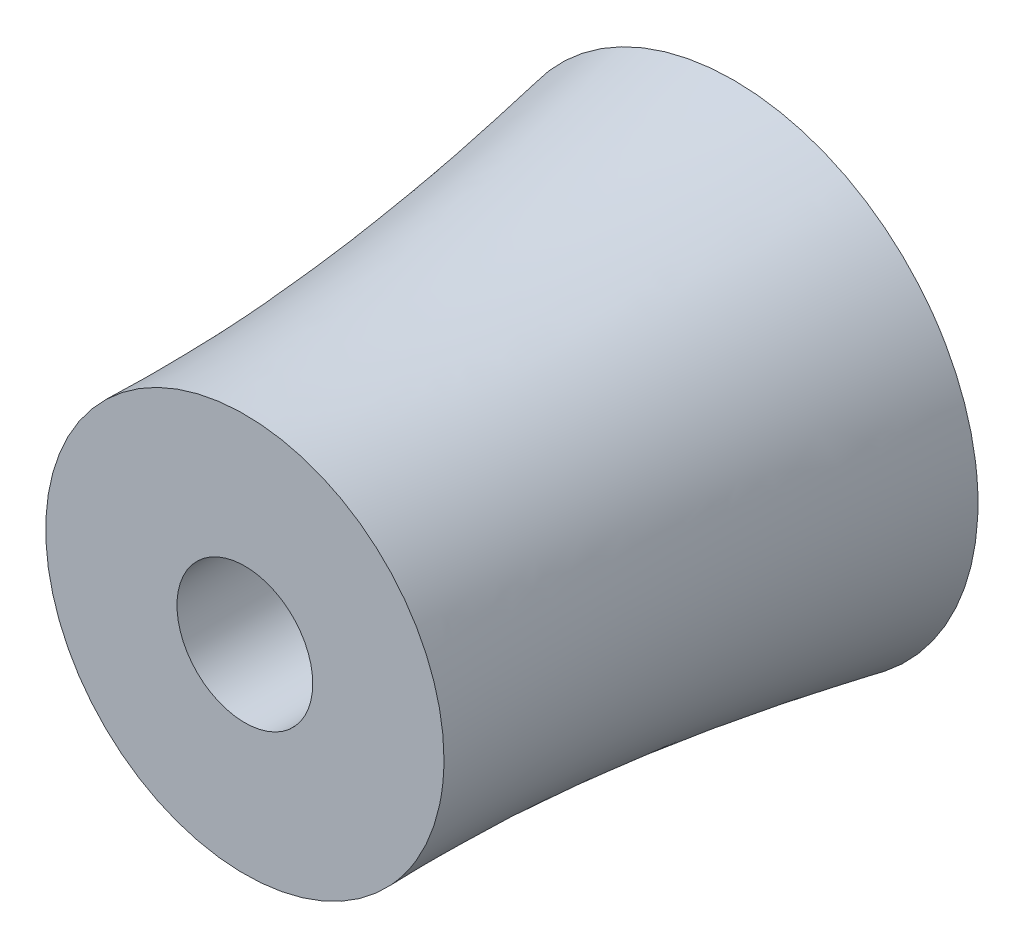
SolidWorks part; units mm, degrees
ref_plane "Plan de face" through (0, 0, 0) normal (0, 0, 1) x (1, 0, 0)
ref_plane "Plan de dessus" through (0, 0, 0) normal (0, 1, 0) x (1, 0, 0)
ref_plane "Plan de droite" through (0, 0, 0) normal (1, 0, 0) x (0, 0, -1)
sketch "Esquisse1" plane through (0, 0, 0) normal (0, 0, 1) x (1, 0, 0)
  circle A0 centre (0, 0) radius 3.75
  circle A1 centre (0, 0) radius 13.5
  dimension "D1" = 7.5
  dimension "D2" = 27
ref_plane "Plan1" through (0, 0, 27) normal (0, 0, 1) x (1, 0, 0)
sketch "Esquisse2" plane through (0, 0, 27) normal (0, 0, 1) x (1, 0, 0)
  circle A0 centre (0, 0) radius 3.75
  circle A1 centre (0, 0) radius 11
  dimension "D1" = 7.5
  dimension "D2" = 22
loft "Lissage1" add section "Esquisse2" section "Esquisse1" start constraint default connector at (-10.2427, 4.0108, 27) connector at (-12.7611, -4.405, 0)
extrude "Enlèv. mat.-Extru.1" cut sketch "Esquisse2<3>" against normal through all contours A0
sketch "Esquisse2<3>" plane through (0, 0, 27) normal (0, 0, 1) x (1, 0, 0) same geometry as "Esquisse2"
